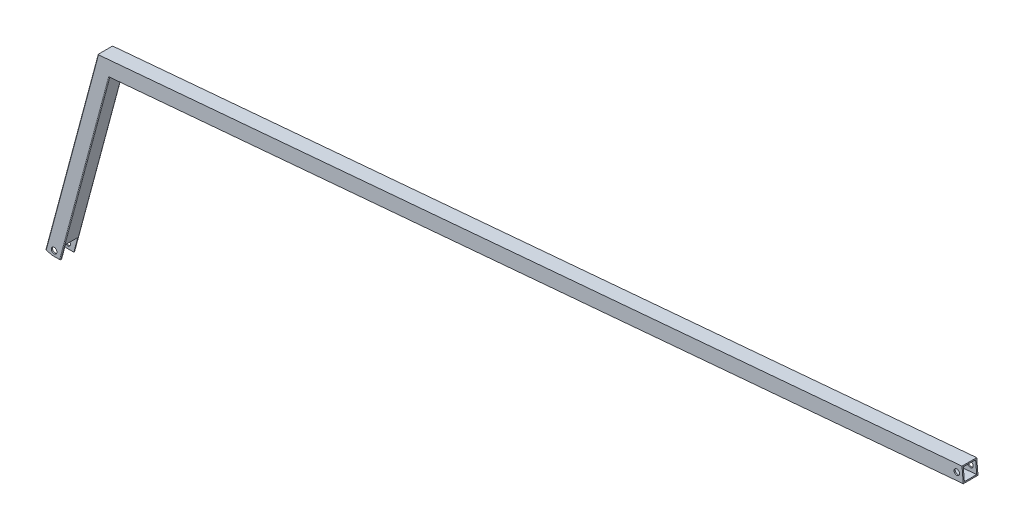
SolidWorks part; units mm, degrees
ref_plane "Front Plane" through (0, 0, 0) normal (0, 0, 1) x (1, 0, 0)
ref_plane "Top Plane" through (0, 0, 0) normal (0, 1, 0) x (1, 0, 0)
ref_plane "Right Plane" through (0, 0, 0) normal (1, 0, 0) x (0, 0, -1)
sketch "Sketch1" plane through (0, 0, 0) normal (0, 0, -1) x (-1, 0, 0)
  line L0 (32.8955, -12.2438) -> (1525.3197, -142.814)
  line L1 (1525.3197, -142.814) -> (1615.5675, -479.6234)
  line L2 (1615.5675, -479.6234) -> (1591.033, -486.1974)
  line L3 (1591.033, -486.1974) -> (1505.3883, -166.5673)
  line L4 (1505.3883, -166.5673) -> (30.6818, -37.5472)
  line L5 (30.6818, -37.5472) -> (32.8955, -12.2438)
  line L6 (22.8132, -24.1102) -> (105.6727, -31.3595) construction
  line L7 (804.8625, -431.8) -> (1577.975, -431.8) construction
  line L8 (1577.975, -298.45) -> (1577.975, -431.8) construction
  line L9 (1592.235, -441.6145) -> (-11348.7172, 47854.6768) construction
  circle A0 centre (41.91, -25.781) radius 4.826
  circle A1 centre (41.91, -25.781) radius 4.8641 construction
  circle A2 centre (1600.835, -473.71) radius 4.826
  circle A3 centre (1600.835, -473.71) radius 3.175 construction
  point P9 (31.7887, -24.8955)
  dimension "D3" = 9.652
  dimension "D1" = 25.4
  dimension "D2" = 25.4
  dimension "D4" = 10.16
  dimension "D5" = 5
  dimension "D6" = 15
  dimension "D7" = 9.525
extrude "Boss-Extrude1" add sketch "Sketch1" along normal mid plane 25.4 contours A2 | A0 | L3 L4 L5 L0 L1 L2 region at (-41.91, -25.781, 0) region at (-1600.835, -473.71, 0)
shell "Shell1" thickness 2.0574 removed face at (-31.7887, -24.8955, 0) removed face at (-1605.661, -473.71, -12.7) removed face at (-1603.3003, -482.9104, 0) removed face at (-46.736, -25.781, -12.7)
fillet "Fillet1" radius 1.27 8 edges at (-1568.6427, -312.447, -10.6426) (-1568.6427, -312.447, 10.6426) (-1550.0115, -325.1541, -10.6426) (-1550.0115, -325.1541, 10.6426) (-1548.2107, -326.3824, 12.7) (-1570.4436, -311.2187, 12.7) (-1570.4436, -311.2187, -12.7) (-1548.2107, -326.3824, -12.7)
sketch "Sketch2" plane through (0, 0, -12.7) normal (0, 0, -1) x (-1, 0, 0)
  line L0 (1604.4588, -482.6) -> (1590.0691, -482.6)
  line L1 (1614.3408, -479.9521) -> (1592.2597, -485.8687) construction
  line L2 (-57.15, -482.6) -> (1616.075, -482.6) construction
  line L3 (1591.033, -486.1974) -> (1505.3883, -166.5673) construction
  line L4 (1590.0691, -482.6) -> (1591.033, -486.1974)
  line L5 (1591.033, -486.1974) -> (1604.4588, -482.6)
extrude "Cut-Extrude1" cut sketch "Sketch2" against normal through all
sketch "Sketch3" plane through (0, 0, 0) normal (1, 0, 0) x (0, 0, -1)
  line L1 (10.6426, -482.6) -> (-10.6426, -482.6)
  line L2 (10.6426, -482.6) -> (10.6426, -457.2)
  line L3 (10.6426, -457.2) -> (-10.6426, -457.2)
  line L4 (-10.6426, -482.6) -> (-10.6426, -457.2)
  line L5 (-4.6736, -462.28) -> (4.6736, -462.28) construction
  line L6 (0, -1000) -> (0, 49000) construction
  line L7 (762, -482.6) -> (-1635.125, -482.6) construction
  line L10 (-10.6426, -478.536) -> (-10.6426, -468.884) construction
  dimension "D1" = 5.08
extrude "Cut-Extrude2" cut sketch "Sketch3" against normal through all
fillet "Fillet2" radius 1.27 4 edges at (-1607.8368, -457.2, -10.6426) (-1584.9855, -457.2, -10.6426) (-1607.8368, -457.2, 10.6426) (-1584.9855, -457.2, 10.6426)
